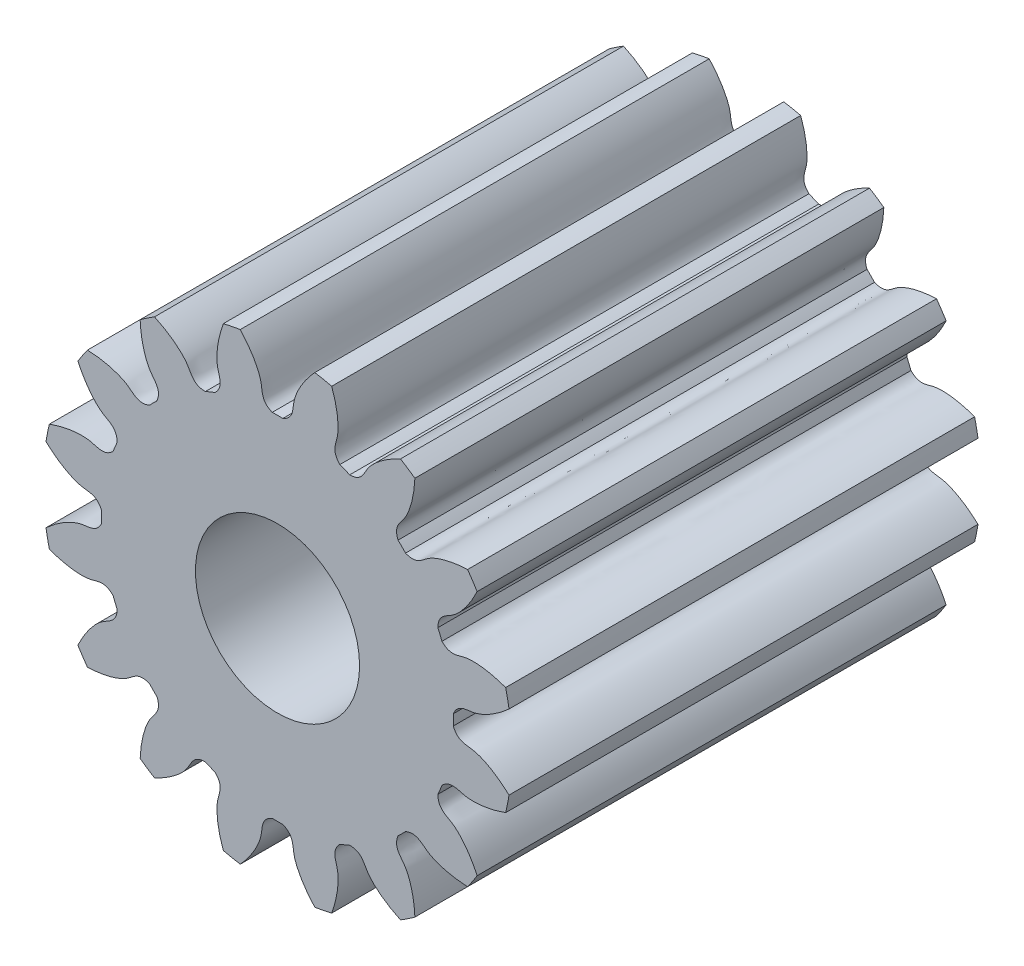
SolidWorks part; units mm, degrees
ref_plane "前视基准面" through (0, 0, 0) normal (0, 0, 1) x (1, 0, 0)
ref_plane "上视基准面" through (0, 0, 0) normal (0, 1, 0) x (1, 0, 0)
ref_plane "右视基准面" through (0, 0, 0) normal (1, 0, 0) x (0, 0, -1)
other "Configuration Table"
sketch "草图1" plane through (0, 0, 0) normal (0, 0, 1) x (1, 0, 0)
  circle A0 centre (0, 0) radius 4.5
extrude "凸台-拉伸1" add sketch "草图1" along normal blind 9
ref_axis "基准轴1" through (0, 0, 9) along (0, 0, -1)
sketch "草图2" plane through (0, 0, 0) normal (0, 0, 1) x (1, 0, 0)
  line L0 (0, 0) -> (0, 4.5) construction
  circle A0 centre (0, 0) radius 4.5 construction
  arc A1 (0.1017, 3.3735) -> (-0.1017, 3.3735) centre (0, 0) ccw
  arc A2 (1.5609, 5.0814) -> (-1.5609, 5.0814) centre (0, 0) ccw
  spline S0 degree 3 poles (0.1017, 3.3735) (0.3209, 3.4651) (0.2847, 3.6353) (0.3224, 3.7934) (0.3256, 3.8058) (0.3295, 3.8195) (0.334, 3.8346) (0.3394, 3.8511) (0.3455, 3.8688) (0.3526, 3.8879) (0.3605, 3.9082) (0.3695, 3.9297) (0.3794, 3.9524) (0.3905, 3.9763) (0.4027, 4.0013) (0.4161, 4.0274) (0.4307, 4.0545) (0.4466, 4.0827) (0.4638, 4.1118) (0.4823, 4.1419) (0.5023, 4.1728) (0.5238, 4.2046) (0.5467, 4.2372) (0.5712, 4.2705) (0.5973, 4.3045) (0.6249, 4.3392) (0.6543, 4.3744) (0.6853, 4.4102) (0.718, 4.4465) (0.7524, 4.4833) (0.7887, 4.5204) (0.8267, 4.5578) (0.8666, 4.5955) (0.9084, 4.6334) (0.952, 4.6715) (0.9975, 4.7096) (1.045, 4.7478) (1.0944, 4.7859) (1.1457, 4.8239) (1.1991, 4.8618) (1.2544, 4.8994) (1.3117, 4.9367) (1.3711, 4.9737) (1.4537, 5.023) (1.5175, 5.0584) (1.5609, 5.0814) knots 0 0 0 0 0.200958 0.205848 0.21139 0.217584 0.224431 0.231929 0.240079 0.248881 0.258335 0.268441 0.2792 0.29061 0.302672 0.315386 0.328753 0.342771 0.357441 0.372764 0.388738 0.405364 0.422643 0.440573 0.459155 0.47839 0.498276 0.518814 0.540005 0.561847 0.584342 0.607488 0.631287 0.655737 0.68084 0.706594 0.733001 0.760059 0.78777 0.816132 0.845147 0.874814 0.905132 0.936103 1 1 1 1
  spline S1 degree 3 poles (-0.1017, 3.3735) (-0.3209, 3.4651) (-0.2847, 3.6353) (-0.3224, 3.7934) (-0.3256, 3.8058) (-0.3295, 3.8195) (-0.334, 3.8346) (-0.3394, 3.8511) (-0.3455, 3.8688) (-0.3526, 3.8879) (-0.3605, 3.9082) (-0.3695, 3.9297) (-0.3794, 3.9524) (-0.3905, 3.9763) (-0.4027, 4.0013) (-0.4161, 4.0274) (-0.4307, 4.0545) (-0.4466, 4.0827) (-0.4638, 4.1118) (-0.4823, 4.1419) (-0.5023, 4.1728) (-0.5238, 4.2046) (-0.5467, 4.2372) (-0.5712, 4.2705) (-0.5973, 4.3045) (-0.6249, 4.3392) (-0.6543, 4.3744) (-0.6853, 4.4102) (-0.718, 4.4465) (-0.7524, 4.4833) (-0.7887, 4.5204) (-0.8267, 4.5578) (-0.8666, 4.5955) (-0.9084, 4.6334) (-0.952, 4.6715) (-0.9975, 4.7096) (-1.045, 4.7478) (-1.0944, 4.7859) (-1.1457, 4.8239) (-1.1991, 4.8618) (-1.2544, 4.8994) (-1.3117, 4.9367) (-1.3711, 4.9737) (-1.4537, 5.023) (-1.5175, 5.0584) (-1.5609, 5.0814) knots 0 0 0 0 0.200958 0.205848 0.21139 0.217584 0.224431 0.231929 0.240079 0.248881 0.258335 0.268441 0.2792 0.29061 0.302672 0.315386 0.328753 0.342771 0.357441 0.372764 0.388738 0.405364 0.422643 0.440573 0.459155 0.47839 0.498276 0.518814 0.540005 0.561847 0.584342 0.607488 0.631287 0.655737 0.68084 0.706594 0.733001 0.760059 0.78777 0.816132 0.845147 0.874814 0.905132 0.936103 1 1 1 1
extrude "切除-拉伸1" cut sketch "草图2" along normal through all
pattern_circular "阵列(圆周)1" count 16 every 22.5 about axis through (0, 0, 9) along (0, 0, -1) of "切除-拉伸1"
sketch "草图3" plane through (0, 0, 0) normal (0, 0, 1) x (1, 0, 0)
  circle A0 centre (0, 0) radius 4 construction
  dimension "Dn" = 8
sketch "草图4" plane through (0, 0, 9) normal (0, 0, 1) x (1, 0, 0)
  circle A0 centre (0, 0) radius 1.575
  dimension "D1" = 3.15
extrude "切除-拉伸2" cut sketch "草图4" against normal blind 10
